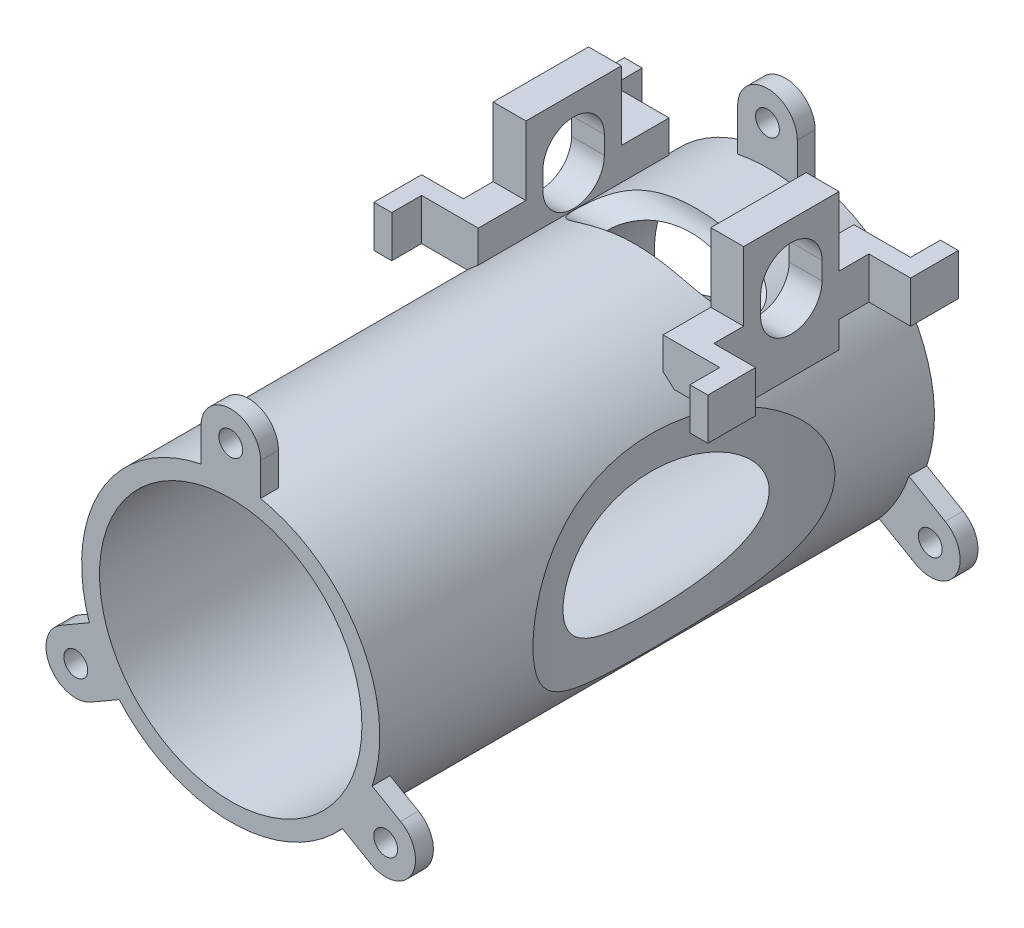
SolidWorks part; units mm, degrees
ref_plane "Front Plane" through (0, 0, 0) normal (0, 0, 1) x (1, 0, 0)
ref_plane "Top Plane" through (0, 0, 0) normal (0, 1, 0) x (1, 0, 0)
ref_plane "Right Plane" through (0, 0, 0) normal (1, 0, 0) x (0, 0, -1)
sketch "Sketch1" plane through (0, 0, 0) normal (0, 0, 1) x (1, 0, 0)
  circle A0 centre (0, 0) radius 22
  circle A1 centre (0, 0) radius 25
  dimension "D1" = 44
  dimension "D2" = 3
extrude "Boss-Extrude1" add sketch "Sketch1" along normal blind 40
ref_plane "Plane1" through (0, 0, 20) normal (0, 0, 1) x (1, 0, 0)
sketch "Sketch3" plane through (0, 0, 0) normal (1, 0, 0) x (0, 0, -1)
  line L0 (0, 25) -> (-40, 25) construction
  circle A0 centre (-20, 25) radius 5.15
  dimension "D1" = 10.3
extrude "Cut-Extrude1" cut sketch "Sketch3" against normal mid plane 50
sketch "Sketch7" plane through (0, 0, 40) normal (0, 0, 1) x (1, 0, 0)
  circle A0 centre (0, 0) radius 22
  circle A1 centre (0, 0) radius 25
extrude "Boss-Extrude4" add sketch "Sketch7" along normal blind 53
ref_plane "Plane2" through (-25, 0, 0) normal (-1, 0, 0) x (0, 0, 1)
sketch "Sketch9" plane through (0, 0, 0) normal (0, 0, -1) x (-1, 0, 0)
  line L0 (0, 0) -> (0, 31.533) construction
  line L1 (-5, 31.533) -> (-5, 24.4949)
  line L2 (5, 31.533) -> (5, 24.4949)
  circle A0 centre (0, 31.533) radius 2
  circle A1 centre (0, 31.533) radius 5
  circle A2 centre (0, 0) radius 25 construction
  arc A3 (-5, 24.4949) -> (5, 24.4949) centre (0, 0) cw
  circle A6 centre (0, 31.533) radius 2 construction
  circle M3 centre (0, 0) radius 25
  dimension "D1" = 4
  dimension "D2" = 3
extrude "Boss-Extrude5" add sketch "Sketch9" against normal blind 3 contours A1 L1 M3 | A1 A3 A0 M3 | A1 L2 M3 region at (0, 26.4396, 0) region at (0, 36.3916, 0)
pattern_circular "CirPattern1" count 3 every 120 about axis through (0, 0, 0) along (0, 0, 1) of "Boss-Extrude5"
sketch "Sketch10" plane through (0, 0, 93) normal (0, 0, 1) x (1, 0, 0)
  line L0 (-5, 30) -> (-5, 24.4949)
  line L1 (5, 30) -> (5, 24.4949)
  line L2 (0, 0) -> (0, 30) construction
  circle A0 centre (0, 30) radius 2
  circle A1 centre (0, 30) radius 5
  arc A2 (-5, 24.4949) -> (5, 24.4949) centre (0, 0) cw
  circle A3 centre (0, 0) radius 25 construction
  circle M5 centre (0, 0) radius 25
  dimension "D2" = 4
  dimension "D3" = 30
  dimension "D1" = 3
extrude "Boss-Extrude6" add sketch "Sketch10" against normal blind 3 contours A1 A0 M5 | A1 L0 M5 | A1 L1 M5 region at (-3.8655, 25.9455, 93) region at (0, 34.8586, 93) region at (3.8655, 25.9455, 93)
pattern_circular "CirPattern2" count 3 every 120 about axis through (0, 0, 93) along (0, 0, 1) of "Boss-Extrude6"
ref_plane "Plane3" through (0, 11.51, 0) normal (0, 1, 0) x (1, 0, 0)
sketch "Sketch14" plane through (0, 0, 20) normal (0, 0, 1) x (1, 0, 0)
  line L0 (-21, 13.5647) -> (-21, 36.5647)
  line L1 (-21, 36.5647) -> (-15.5, 36.5647)
  line L2 (-15.5, 36.5647) -> (-15.5, 19.615)
  line L3 (-25, 27.5) -> (-25, -27.5) construction
  arc A0 (-5, 24.4949) -> (-23.7132, -7.9173) centre (0, 0) ccw construction
  arc A1 (-15.5, 19.615) -> (-21, 13.5647) centre (0, 0) ccw
  dimension "D1" = 23
  dimension "D2" = 4
  dimension "D3" = 5.5
extrude "Boss-Extrude7" add sketch "Sketch14" along normal mid plane 16
sketch "Sketch15" plane through (-21, 0, 0) normal (-1, 0, 0) x (0, 0, 1)
  line L0 (20, 25) -> (20, 28) construction
  line L1 (20, -27.5) -> (20, 27.5) construction
  line L2 (14.85, 25) -> (14.85, 28)
  line L3 (25.15, 25) -> (25.15, 28)
  line L4 (90, 25) -> (25.15, 25) construction
  arc A0 (14.85, 25) -> (25.15, 25) centre (20, 25) ccw
  arc A1 (25.15, 28) -> (14.85, 28) centre (20, 28) ccw
  point P4 (20, 26.5)
  point P9 (0, 0)
  dimension "D1" = 5.15
  dimension "D2" = 3
extrude "Cut-Extrude5" cut sketch "Sketch15" against normal blind 16
ref_plane "Plane5" through (0, 25, 0) normal (0, 1, 0) x (1, 0, 0)
sketch "Sketch17" plane through (0, 25, 0) normal (0, 1, 0) x (1, 0, 0)
  line L1 (-15.5, -28) -> (-21, -28)
  line L2 (-15.5, -28) -> (-15.5, -33)
  line L3 (-15.5, -33) -> (-21, -33)
  line L4 (-21, -28) -> (-21, -33)
  line L5 (-15.5, -28) -> (-21, -33) construction
  line L6 (-15.5, -33) -> (-21, -28) construction
  line L7 (-15.5, -33) -> (-28, -33)
  line L8 (-15.5, -33) -> (-15.5, -36)
  line L9 (-15.5, -36) -> (-28, -36)
  line L10 (-28, -33) -> (-28, -36)
  line L11 (-15.5, -33) -> (-28, -36) construction
  line L12 (-15.5, -36) -> (-28, -33) construction
  line L13 (-28, -36) -> (-25, -36)
  line L14 (-28, -36) -> (-28, -41)
  line L15 (-28, -41) -> (-25, -41)
  line L16 (-25, -36) -> (-25, -41)
  line L17 (-28, -36) -> (-25, -41) construction
  line L18 (-28, -41) -> (-25, -36) construction
  point P4 (-18.25, -30.5)
  point P10 (-21.75, -34.5)
  point P14 (-26.5, -38.5)
  point P15 (-30.9756, -33)
  dimension "D1" = 5
  dimension "D2" = 3
  dimension "D3" = 5
  dimension "D4" = 4
extrude "Boss-Extrude8" add sketch "Sketch17" against normal blind 7 contours L16 L9 L14 L15 | L7 L10 L9 L8 L3 | L1 L4 L3 L2 region at (-18.25, 25, 30.5) region at (-21.75, 25, 34.5) region at (-26.5, 25, 38.5)
mirror "Mirror1" about plane through (0, 0, 20) normal (0, 0, 1) of "Boss-Extrude8"
mirror "Mirror2" about plane through (0, 0, 0) normal (1, 0, 0) of "Mirror1", "Boss-Extrude8", "Cut-Extrude5", "Boss-Extrude7"
sketch "Sketch12" plane through (0, 11.51, 0) normal (0, 1, 0) x (1, 0, 0)
  line L0 (0, -44.5194) -> (0, -33.7673) construction
  line L1 (-24.8084, 0) -> (-32.3084, 0) construction
  circle A0 centre (-80.5, -42) radius 60
  circle A1 centre (80.5, -42) radius 60
  circle A2 centre (-80.5, -42) radius 61
  circle A3 centre (80.5, -42) radius 61
  point P7 (0, 0)
  dimension "D1" = 120
  dimension "D2" = 161
  dimension "D3" = 42
  dimension "D4" = 1
extrude "Cut-Extrude4" cut sketch "Sketch12" against normal blind 41 and the other way blind 6 contours A2 A0 | A1 | A3 A1 | A0 region at (80.5, 11.51, 42) region at (-141.3275, 11.51, 42) region at (19.6725, 11.51, 42)
